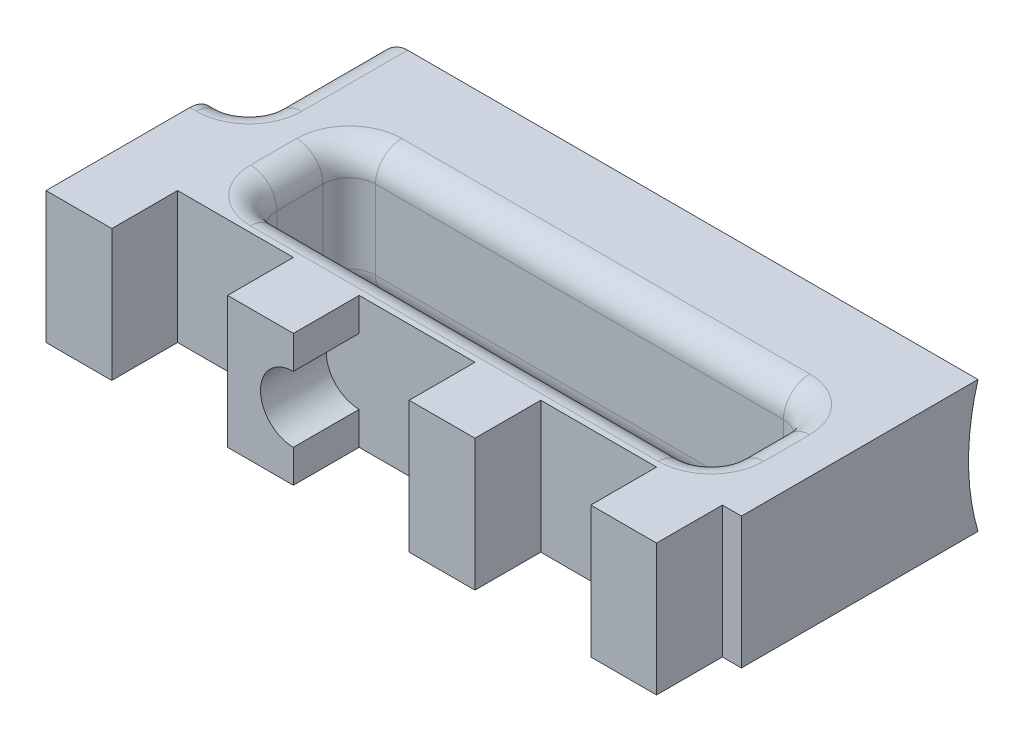
SolidWorks part; units mm, degrees
ref_plane "Front Plane" through (0, 0, 0) normal (0, 0, 1) x (1, 0, 0)
ref_plane "Top Plane" through (0, 0, 0) normal (0, 1, 0) x (1, 0, 0)
ref_plane "Right Plane" through (0, 0, 0) normal (1, 0, 0) x (0, 0, -1)
sketch "Sketch1" plane through (0, 0, 0) normal (0, 1, 0) x (1, 0, 0)
  line L0 (0, 22.225) -> (0, -22.225) construction
  line L1 (28.6599, -20.131) -> (26.8197, -20.131)
  line L2 (28.6599, -20.131) -> (28.6599, 17.969)
  line L3 (28.6599, 17.969) -> (-28.8983, 17.969)
  line L4 (-32.1083, 12.8512) -> (-32.1083, -20.131)
  line L5 (-28.8983, 12.8512) -> (-32.1083, 12.8512)
  line L6 (28.6599, 17.969) -> (-32.1083, -20.131) construction
  line L7 (22.6216, -17.0219) -> (-21.8284, -17.0219)
  line L8 (22.6216, -17.0219) -> (22.6216, -7.4969)
  line L9 (22.6216, -7.4969) -> (-21.8284, -7.4969)
  line L10 (-14.5823, -26.481) -> (-8.2323, -26.481)
  line L12 (-32.1083, -20.131) -> (-32.1083, -26.481)
  line L13 (-32.1083, -26.481) -> (-25.7583, -26.481)
  line L14 (-25.7583, -20.131) -> (-25.7583, -26.481)
  line L15 (-14.5823, -20.131) -> (-14.5823, -26.481)
  line L16 (-8.2323, -20.131) -> (-8.2323, -26.481)
  line L17 (2.9437, -26.481) -> (9.2937, -26.481)
  line L18 (2.9437, -20.131) -> (2.9437, -26.481)
  line L19 (9.2937, -20.131) -> (9.2937, -26.481)
  line L20 (20.4697, -26.481) -> (26.8197, -26.481)
  line L21 (20.4697, -20.131) -> (20.4697, -26.481)
  line L22 (26.8197, -20.131) -> (26.8197, -26.481)
  line L23 (-32.1083, -26.481) -> (-14.5823, -26.481) construction
  line L24 (-21.8284, -17.0219) -> (-21.8284, -7.4969)
  line L26 (-28.8983, 12.8512) -> (-28.8983, 17.969)
  line L27 (-14.5823, -20.131) -> (-25.7583, -20.131)
  line L28 (2.9437, -20.131) -> (-8.2323, -20.131)
  line L29 (20.4697, -20.131) -> (9.2937, -20.131)
  point P0 (0, 0)
  point P30 (0.3966, -7.4969)
  dimension "D4" = 6.35
  dimension "D5" = 6.35
  dimension "D6" = 0
  dimension "D8" = 17.526
  dimension "D3" = 44.45
  dimension "D9" = 9.525
  dimension "D7" = 4
extrude "Boss-Extrude1" add sketch "Sketch1" along normal blind 12.7 contours L29 L21 L20 L22 L1 L2 L3 L26 L12 L13 L14 L27 L15 L10 L16 L28 L18 L17 L19 L7 L24 L9 L8 region at (-2.0058, 0, 0.6503)
sketch "Sketch2" plane through (28.6599, 0, 0) normal (1, 0, 0) x (0, 0, -1)
  line L1 (-20.131, 12.7) -> (17.969, 12.7) construction
  line L2 (-20.131, 0) -> (17.969, 0) construction
  line L3 (2.7026, 12.7) -> (17.969, 12.7)
  line L4 (17.969, 12.7) -> (17.969, 0)
  line L6 (-20.131, 6.35) -> (24.319, 6.35) construction
  line L7 (-20.131, 12.7) -> (-20.131, 0) construction
  line L9 (17.969, 0) -> (2.7026, 0)
  arc A0 (2.7026, 12.7) -> (2.7026, 0) centre (24.319, 6.35) ccw
fillet "Fillet1" radius 2.54 4 edges at (22.6216, 6.35, 17.0219) (22.6216, 6.35, 7.4969) (-21.8284, 6.35, 7.4969) (-21.8284, 6.35, 17.0219)
fillet "Fillet2" radius 2.54 16 edges at (21.8777, 0, 16.278) (22.6216, 0, 12.2594) (21.8777, 0, 8.2409) (0.3966, 0, 7.4969) (-21.0844, 0, 8.2409) (-21.8284, 0, 12.2594) (-21.0844, 0, 16.278) (21.8777, 12.7, 8.2409) (22.6216, 12.7, 12.2594) (21.8777, 12.7, 16.278) (0.3966, 12.7, 17.0219) (-21.0844, 12.7, 16.278) (-21.8284, 12.7, 12.2594) (-21.0844, 12.7, 8.2409) (0.3966, 0, 17.0219) (0.3966, 12.7, 7.4969)
sketch "Sketch3" plane through (0, 0, 26.481) normal (0, 0, 1) x (1, 0, 0)
  line L0 (-8.2323, 12.7) -> (-8.2323, 0) construction
  line L1 (-8.2323, 12.7) -> (-8.2323, 0) construction
  line L2 (-8.2323, 9.525) -> (-8.2323, 3.175)
  arc A0 (-8.2323, 9.525) -> (-8.2323, 3.175) centre (-8.2323, 6.35) ccw
extrude "Cut-Extrude2" cut sketch "Sketch3" against normal up to surface (6.35 mm away) up to face at (-2.6443, 6.35, 20.131)
extrude "Cut-Extrude6" cut sketch "Sketch2" against normal through all
sketch "Sketch4" plane through (-32.1083, 0, 0) normal (-1, 0, 0) x (0, 0, 1)
  line L0 (26.481, 6.35) -> (-24.319, 6.35) construction
  line L1 (26.481, 12.7) -> (26.481, 0) construction
  line L2 (-2.7026, 12.7) -> (26.481, 12.7) construction
  line L3 (-2.7026, 0) -> (26.481, 0) construction
  line L4 (0.5367, 0) -> (-10.2407, 0)
  line L5 (-10.2407, 0) -> (-10.2407, 12.7)
  line L6 (-10.2407, 12.7) -> (0.5367, 12.7)
  arc A0 (0.5367, 12.7) -> (0.5367, 0) centre (-24.319, 6.35) cw
  dimension "D1" = 50.8
extrude "Cut-Extrude7" cut sketch "Sketch4" against normal blind 3.175
sketch "Sketch5" plane through (-32.1083, 0, 0) normal (-1, 0, 0) x (0, 0, 1)
  line L0 (0.5367, 0) -> (26.481, 0) construction
  line L1 (0.5367, 12.7) -> (10.0617, 12.7)
  line L2 (0.5367, 12.7) -> (0.5367, 0)
  line L3 (0.5367, 0) -> (10.0617, 0)
  line L4 (10.0617, 12.7) -> (10.0617, 0)
  dimension "D1" = 9.525
extrude "Cut-Extrude8" cut sketch "Sketch5" against normal blind 3.175
fillet "Fillet3" radius 2.54 5 edges at (-28.9333, 0, 3.6796) (-28.9333, 12.7, 3.6796) (-30.5208, 0, 10.0617) (-28.9333, 6.35, 10.0617) (-30.5208, 12.7, 10.0617)
